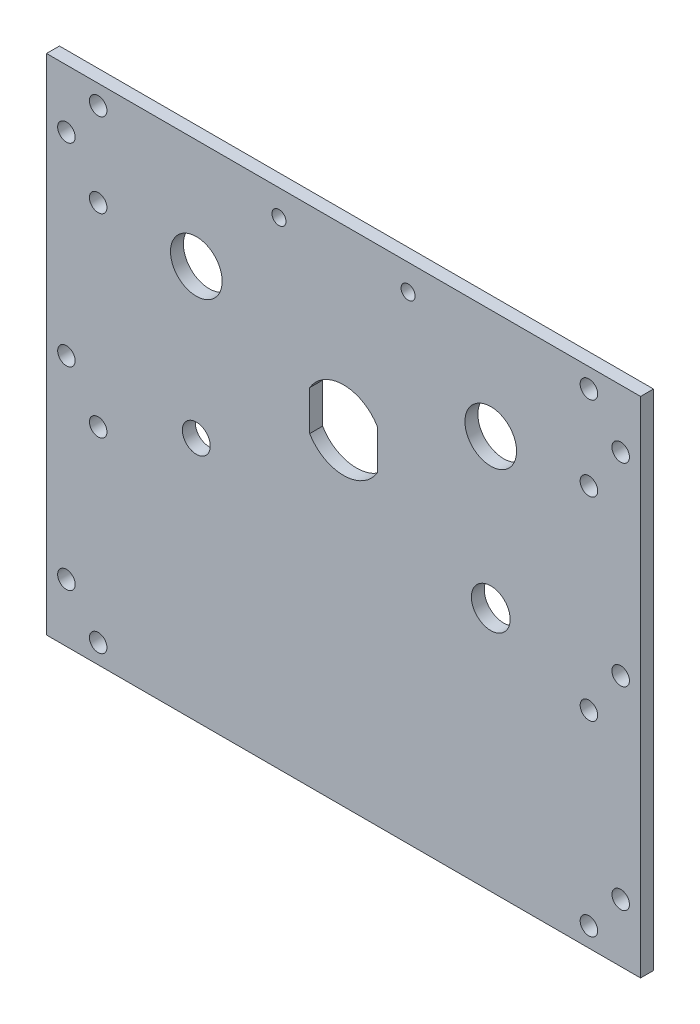
SolidWorks part; units mm, degrees
ref_plane "Front Plane" through (0, 0, 0) normal (0, 0, 1) x (1, 0, 0)
ref_plane "Top Plane" through (0, 0, 0) normal (0, 1, 0) x (1, 0, 0)
ref_plane "Right Plane" through (0, 0, 0) normal (1, 0, 0) x (0, 0, -1)
sketch "Sketch1" plane through (0, 0, 0) normal (0, 0, 1) x (1, 0, 0)
  line L8 (0, 123.825) -> (-146.05, 123.825)
  line L9 (-146.05, 123.825) -> (-146.05, 0)
  line L10 (-146.05, 0) -> (0, 0)
  line L11 (0, 0) -> (0, 123.825)
extrude "Boss-Extrude1" add sketch "Sketch1" against normal blind 3.175
hole_wizard "#6 Clearance Hole1" positions "Sketch3" profile "Sketch2" hole size "#6" standard "ANSI Inch" end condition through all
sketch "Sketch3" plane through (0, 0, -3.175) normal (0, 0, -1) x (-1, 0, 0)
  line L0 (88.9, 117.475) -> (57.15, 117.475) construction
  point P0 (12.7, 119.0625)
  point P9 (133.35, 119.0625)
  point P12 (141.1605, 109.5375)
  point P15 (133.35, 98.425)
  point P18 (141.1605, 61.9125)
  point P21 (133.35, 50.673)
  point P24 (133.35, 4.7625)
  point P27 (12.7, 4.7625)
  point P30 (12.7, 50.673)
  point P33 (12.7, 98.425)
  point P36 (4.8895, 109.5375)
  point P39 (141.1605, 14.2875)
  point P42 (4.8895, 14.2875)
  point P45 (4.8895, 61.9125)
sketch "Sketch2" plane through (-12.7, 119.0625, -3.175) normal (1, 0, 0) x (0, 1, 0)
  line L0 (0, 0) -> (0, 3.175)
  line L1 (0, 3.175) -> (2.1526, 3.175)
  line L2 (2.1526, 3.175) -> (2.1526, 0)
  line L5 (2.1526, 0) -> (0, 0)
  line L11 (0, -6.35) -> (0, 107.95) construction
  dimension "Thru Hole Dia." = 4.3053
  dimension "Thru Hole Depth" = 3.175
sketch "Sketch4" plane through (0, 0, -3.175) normal (0, 0, -1) x (-1, 0, 0)
  line L2 (81.3435, 85.0323) -> (81.3435, 75.2417)
  line L3 (64.7065, 75.2417) -> (64.7065, 85.0323)
  circle A0 centre (36.83, 96.901) radius 6.35
  circle A1 centre (36.83, 60.325) radius 4.7625
  circle A2 centre (109.22, 60.325) radius 3.429
  circle A3 centre (109.22, 96.901) radius 6.35
  arc A6 (81.3435, 85.0323) -> (64.7065, 85.0323) centre (73.025, 80.137) ccw
  arc A7 (64.7065, 75.2417) -> (81.3435, 75.2417) centre (73.025, 80.137) ccw
  dimension "D1" = 9.525
  dimension "D2" = 12.7
  dimension "D3" = 6.858
extrude "Cut-Extrude1" cut sketch "Sketch4" against normal through all
hole_wizard "#4 Clearance Hole1" positions "Sketch6" profile "Sketch5" hole size "#4" standard "ANSI Inch" end condition through all
sketch "Sketch6" plane through (0, 0, 0) normal (0, 0, 1) x (1, 0, 0)
  point P3 (-88.9, 117.475)
  point P6 (-57.15, 117.475)
sketch "Sketch5" plane through (-88.9, 117.475, 0) normal (1, 0, 0) x (0, -1, 0)
  line L0 (0, 0) -> (0, 3.175)
  line L1 (0, 3.175) -> (1.7272, 3.175)
  line L2 (1.7272, 3.175) -> (1.7272, 0)
  line L5 (1.7272, 0) -> (0, 0)
  line L11 (0, -6.35) -> (0, 107.95) construction
  dimension "Thru Hole Dia." = 3.4544
  dimension "Thru Hole Depth" = 3.175
